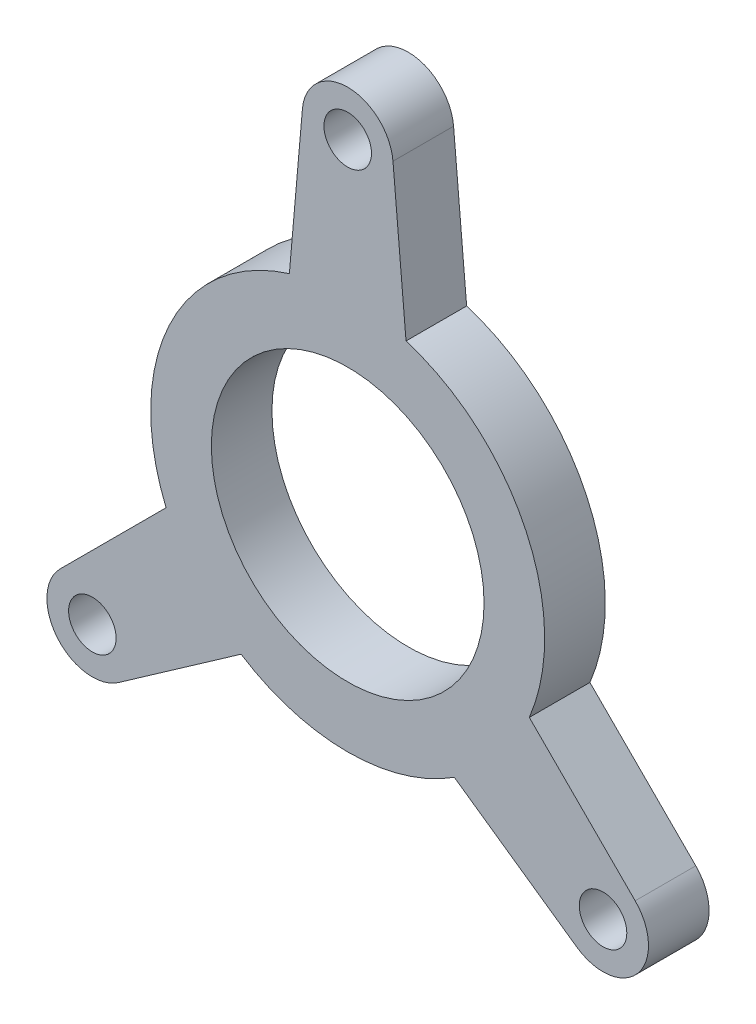
SolidWorks part; units mm, degrees
material "6061-T6 (SS)"
ref_plane "Front Plane" through (0, 0, 0) normal (0, 0, 1) x (1, 0, 0)
ref_plane "Top Plane" through (0, 0, 0) normal (0, 1, 0) x (1, 0, 0)
ref_plane "Right Plane" through (0, 0, 0) normal (1, 0, 0) x (0, 0, -1)
sketch "Sketch1" plane through (0, 0, 0) normal (0, 0, 1) x (1, 0, 0)
  line L0 (0, 0) -> (0, 34.925) construction
  line L1 (0, 0) -> (26.7541, -22.4494) construction
  line L2 (0, 0) -> (-26.7541, -22.4494) construction
  line L3 (-4.7444, 35.3401) -> (-6.1117, 19.7118)
  line L4 (4.7444, 35.3401) -> (6.1117, 19.7118)
  line L5 (30.1217, -19.0818) -> (19.0286, -7.9887)
  line L6 (24.0224, -26.3506) -> (11.1716, -17.3523)
  line L7 (-24.0224, -26.3506) -> (-11.1716, -17.3523)
  line L8 (-19.0286, -7.9887) -> (-30.1217, -19.0818)
  circle A0 centre (26.7541, -22.4494) radius 4.7625
  circle A1 centre (0, 34.925) radius 4.7625
  circle A2 centre (-26.7541, -22.4494) radius 4.7625
  circle A3 centre (26.7541, -22.4494) radius 2.4892
  circle A4 centre (-26.7541, -22.4494) radius 2.4892
  circle A5 centre (0, 34.925) radius 2.4892
  circle A6 centre (0, 0) radius 14.2875
  circle A7 centre (0, 0) radius 20.6375
  dimension "D1" = 9.525
  dimension "D4" = 4.9784
  dimension "D13" = 6.35
  dimension "D14" = 28.575
  dimension "D2" = 34.925
  dimension "D5" = 130
  dimension "D6" = 130
  dimension "D7" = 5
  dimension "D8" = 5
  dimension "D9" = 5
  dimension "D10" = 5
  dimension "D11" = 5
  dimension "D12" = 5
extrude "Boss-Extrude1" add sketch "Sketch1" along normal mid plane 6.35 contours A7 A6 | A7 L4 A1 L3 | A7 L6 A0 L5 | A7 L8 A2 L7 | A2 A4 | A1 A5 | A0 A3 region at (0, 25.7229, 0) region at (0, 39.5528, 0) region at (0, 20.0538, 0) region at (-19.7049, -16.5343, 0) region at (-24.9831, -18.1738, 0) region at (19.7049, -16.5343, 0) region at (31.0296, -20.6784, 0)
